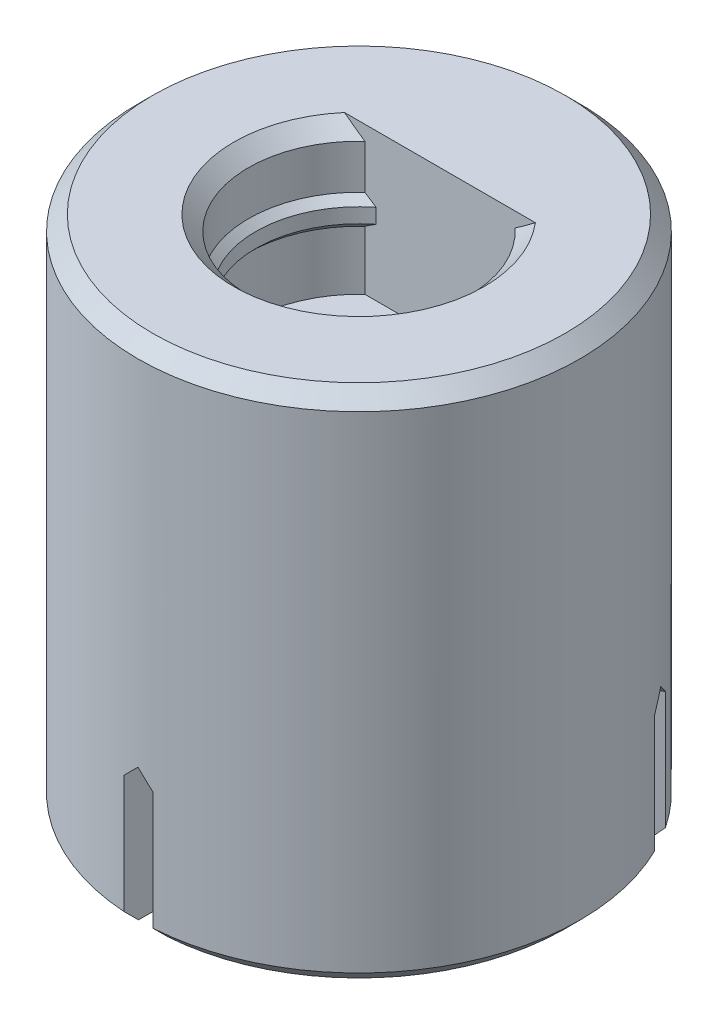
SolidWorks part; units mm, degrees
ref_plane "Front Plane" through (0, 0, 0) normal (0, 0, 1) x (1, 0, 0)
ref_plane "Top Plane" through (0, 0, 0) normal (0, 1, 0) x (1, 0, 0)
ref_plane "Right Plane" through (0, 0, 0) normal (1, 0, 0) x (0, 0, -1)
sketch "Sketch1" plane through (0, 0, 0) normal (0, 1, 0) x (1, 0, 0)
  circle A0 centre (0, 0) radius 15
extrude "Boss-Extrude1" add sketch "Sketch1" along normal blind 35
sketch "Sketch2" plane through (0, 0, 0) normal (0, 0, 1) x (1, 0, 0)
  line L1 (0, 35) -> (0, 0) construction
  line L8 (0, 15) -> (0, 5)
  line L9 (0, 15) -> (6.6332, 15)
  line L10 (0, 5) -> (0, 0)
  line L11 (0, 0) -> (10.9087, 0)
  arc A3 (6.6332, 15) -> (10.9087, 0) centre (0, 5) cw
revolve "Cut-Revolve1" cut sketch "Sketch2" angle 360 about L8
chamfer "Chamfer1" distance 1 angle 45 1 edges at (0, 0, 15)
chamfer "Chamfer2" distance 1 angle 65 1 edges at (0, 0, 10.9087) first distance on face at (0, 15, 6.6332)
sketch "Sketch3" plane through (0, 0, 0) normal (0, 0, 1) x (1, 0, 0)
  line L0 (0, 15) -> (-6.6332, 15)
  line L2 (-6.6332, 15) -> (6.6332, 15) construction
  line L3 (0, 15) -> (0, 21.6332)
  line L4 (0, 21.6332) -> (-6.6332, 15)
revolve "Cut-Revolve2" cut sketch "Sketch3" angle 360 about L3
sketch "Sketch4" plane through (0, 0, 0) normal (0, -1, 0) x (1, 0, 0)
  line L0 (0, 0) -> (0, 17) construction
  line L1 (0, 0) -> (14.7224, -8.5) construction
  line L2 (-14.7224, -8.5) -> (0, 0) construction
  line L3 (0, 17) -> (1, 17)
  line L4 (0, 17) -> (-1, 17)
  line L5 (-14.7224, -8.5) -> (-14.2224, -9.366)
  line L6 (-14.7224, -8.5) -> (-15.2224, -7.634)
  line L7 (14.7224, -8.5) -> (15.2224, -7.634)
  line L8 (14.7224, -8.5) -> (14.2224, -9.366)
  line L9 (0, 0) -> (-1, 0.5774) construction
  line L10 (0, 0) -> (1, 0.5774) construction
  line L11 (0, 0) -> (0, -1.1547) construction
  line L12 (-15.2224, -7.634) -> (-1, 0.5774)
  line L13 (-1, 0.5774) -> (-1, 17)
  line L14 (1, 17) -> (1, 0.5774)
  line L15 (1, 0.5774) -> (15.2224, -7.634)
  line L16 (14.2224, -9.366) -> (0, -1.1547)
  line L17 (0, -1.1547) -> (-14.2224, -9.366)
extrude "Cut-Extrude1" cut sketch "Sketch4" against normal blind 10 contours L15 L7 L8 L16 L17 L5 L6 L12 L13 L4 L3 L14
chamfer "Chamfer3" distance 1 angle 45 6 edges at (11.6845, 10, -5.5913) (10.6845, 10, -7.3234) (1, 10, 12.9147) (-1, 10, 12.9147) (-10.6845, 10, -7.3234) (-11.6845, 10, -5.5913)
sketch "Sketch5" plane through (0, 35, 0) normal (0, 1, 0) x (1, 0, 0)
  line L0 (0, 7.5) -> (0, 5.5) construction
  line L1 (-5.099, 5.5) -> (5.099, 5.5)
  arc A1 (-5.099, 5.5) -> (5.099, 5.5) centre (0, 0) ccw
extrude "Cut-Extrude2" cut sketch "Sketch5" against normal blind 10 contours A1 L1
ref_plane "SnapFeaturePlane" through (0, 30, 0) normal (0, 1, 0) x (1, 0, 0)
sketch "Sketch6" plane through (0, 30, 0) normal (0, 1, 0) x (1, 0, 0)
  line L0 (0, -7.5) -> (0, -7) construction
  line L1 (-5.099, 5.5) -> (5.099, 5.5) construction
  line L3 (-5.099, 5.5) -> (-4.3301, 5.5)
  line L4 (4.3301, 5.5) -> (5.099, 5.5)
  arc A0 (-5.099, 5.5) -> (5.099, 5.5) centre (0, 0) ccw construction
  arc A1 (0, -7) -> (-4.3301, 5.5) centre (0, 0) cw
  arc A2 (0, -7) -> (4.3301, 5.5) centre (0, 0) ccw
  arc A3 (5.099, 5.5) -> (-5.099, 5.5) centre (0, 0) cw
  arc A4 (-5.099, 5.5) -> (5.099, 5.5) centre (0, 0) ccw construction
extrude "Boss-Extrude2" add sketch "Sketch6" along normal mid plane 2 contours A1 L3 A3 L4 A2
chamfer "Chamfer5" distance 0.5 angle 45 2 edges at (0, 29, 7) (0, 31, 7)
chamfer "Chamfer6" distance 1 angle 45 1 edges at (0, 35, 15)
chamfer "Chamfer7" distance 1 angle 45 1 edges at (0, 35, 7.5)
